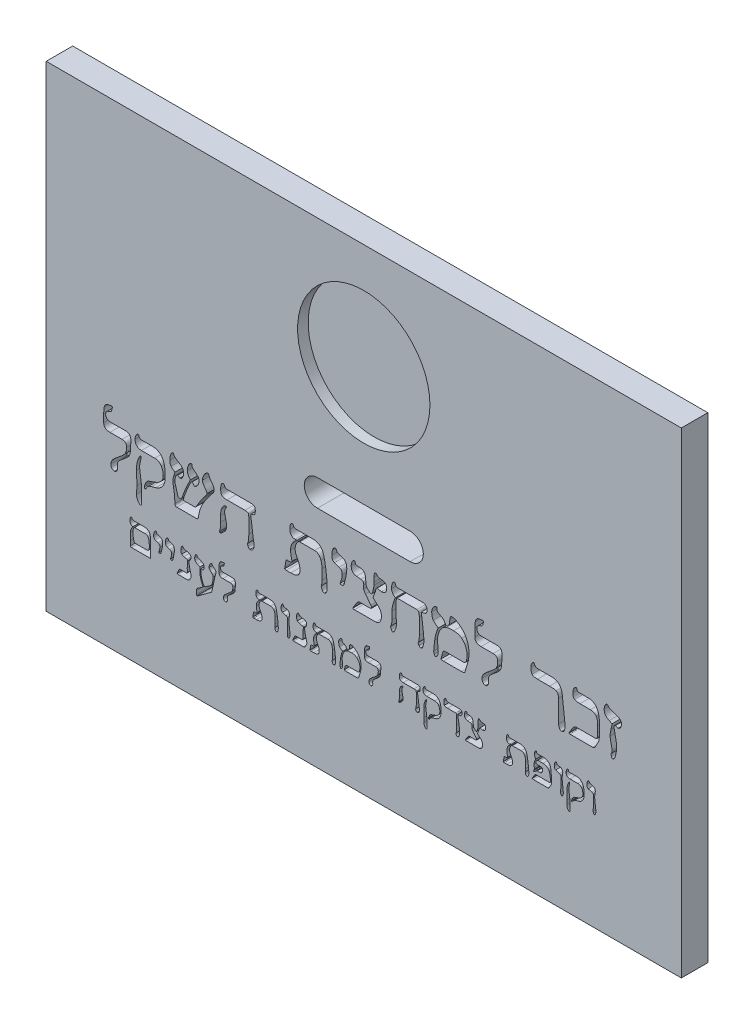
SolidWorks part; units mm, degrees
ref_plane "Front Plane" through (0, 0, 0) normal (0, 0, 1) x (1, 0, 0)
ref_plane "Top Plane" through (0, 0, 0) normal (0, 1, 0) x (1, 0, 0)
ref_plane "Right Plane" through (0, 0, 0) normal (1, 0, 0) x (0, 0, -1)
sketch "Sketch1" plane through (0, 0, 0) normal (0, 0, 1) x (1, 0, 0)
  line L0 (65.0875, 57.15) -> (87.3125, 57.15) construction
  line L1 (0, 0) -> (152.4, 0)
  line L2 (0, 0) -> (0, 114.3)
  line L3 (0, 114.3) -> (152.4, 114.3)
  line L4 (152.4, 0) -> (152.4, 114.3)
  line L5 (65.0875, 60.325) -> (87.3125, 60.325)
  line L6 (65.0875, 53.975) -> (87.3125, 53.975)
  line L7 (0, 114.3) -> (152.4, 0) construction
  line L8 (152.4, 114.3) -> (0, 0) construction
  line L9 (76.2, 57.15) -> (76.2, 88.9) construction
  arc A0 (65.0875, 60.325) -> (65.0875, 53.975) centre (65.0875, 57.15) ccw
  arc A1 (87.3125, 53.975) -> (87.3125, 60.325) centre (87.3125, 57.15) ccw
  point P7 (76.2, 57.15)
  point P15 (76.2, 57.15)
  dimension "D4" = 3.175
  dimension "D1" = 152.4
  dimension "D2" = 114.3
  dimension "D3" = 22.225
  dimension "D6" = 31.75
extrude "Boss-Extrude1" add sketch "Sketch1" along normal blind 6.35
sketch "Sketch2" plane through (0, 0, 0) normal (0, 0, 1) x (1, 0, 0)
  line L10 (0, 37.3144) -> (152.4, 37.3144) construction
  line L11 (0, 23.4923) -> (152.4, 23.4923) construction
  text T0 "וקופת צדקה למתנות לעניים" font "Guttman Drogolin" height 7.62
  text T1 "זכר למחצית השקל" font "Guttman Drogolin" height 12.7
extrude "Cut-Extrude5" cut sketch "Sketch2" against normal blind 3.81 from surface at 6.35 starting at face at (76.2, 57.15, 6.35)
sketch "Sketch5" plane through (0, 0, 6.35) normal (0, 0, 1) x (1, 0, 0)
  line L0 (76.2, 114.3) -> (76.2, 0) construction
  line L1 (152.4, 114.3) -> (0, 114.3) construction
  line L2 (0, 0) -> (152.4, 0) construction
  line L3 (90.4875, 57.15) -> (61.9125, 57.15) construction
  circle A0 centre (76.2, 88.9) radius 15.875
  arc A1 (87.3125, 53.975) -> (87.3125, 60.325) centre (87.3125, 57.15) ccw construction
  arc A2 (65.0875, 60.325) -> (65.0875, 53.975) centre (65.0875, 57.15) ccw construction
  point P16 (76.2, 57.15)
  dimension "D1" = 31.75
  dimension "D2" = 31.75
extrude "Cut-Extrude6" cut sketch "Sketch5" against normal blind 2.54
